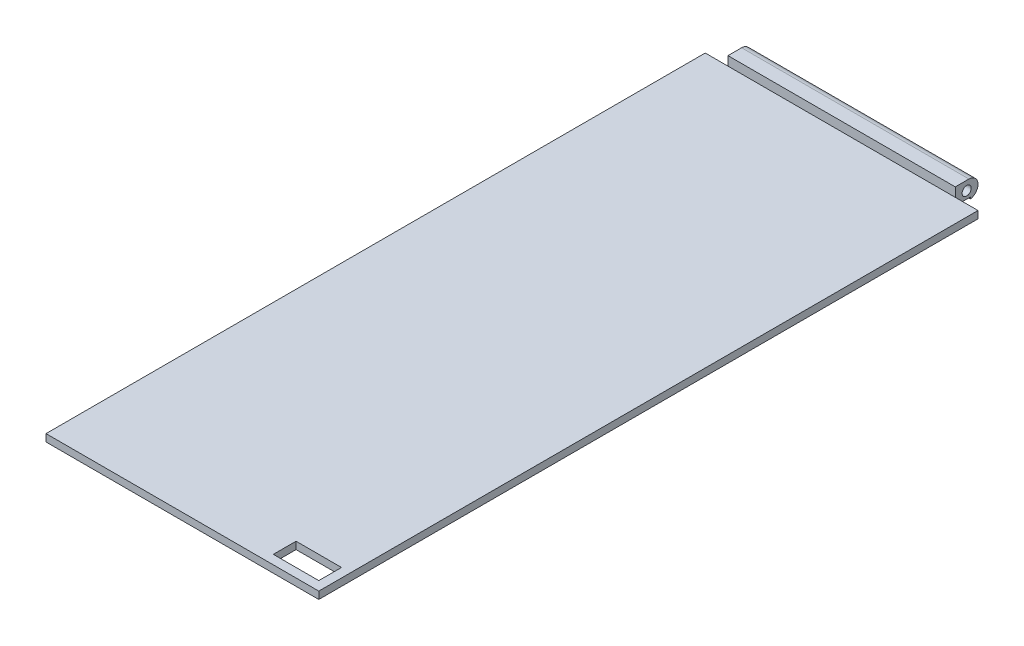
SolidWorks part; units mm, degrees
ref_plane "Front Plane" through (0, 0, 0) normal (0, 0, 1) x (1, 0, 0)
ref_plane "Top Plane" through (0, 0, 0) normal (0, 1, 0) x (1, 0, 0)
ref_plane "Right Plane" through (0, 0, 0) normal (1, 0, 0) x (0, 0, -1)
sketch "Sketch1" plane through (0, 0, 0) normal (0, 1, 0) x (1, 0, 0)
  line L1 (-15, -35) -> (15, -35)
  line L2 (-15, -35) -> (-15, 35)
  line L3 (-15, 35) -> (15, 35)
  line L4 (15, -35) -> (15, 35)
  line L5 (-15, -35) -> (15, 35) construction
  line L6 (-15, 35) -> (15, -35) construction
  point P0 (0, 0)
  dimension "D1" = 70
  dimension "D2" = 30
extrude "Boss-Extrude1" add sketch "Sketch1" along normal blind 1 contours L2 L3 L4 L1
sketch "Sketch2" plane through (0, 1, 0) normal (0, 1, 0) x (1, 0, 0)
  line L0 (15, -35) -> (15, 35) construction
  line L1 (-15, 35) -> (15, 35)
  line L2 (-15, 35) -> (-15, 32.5)
  line L3 (-15, 32.5) -> (15, 32.5)
  line L4 (15, 35) -> (15, 32.5)
  dimension "D1" = 2.5
extrude "Boss-Extrude2" add sketch "Sketch2" along normal blind 1
sketch "Sketch3" plane through (15, 0, 0) normal (1, 0, 0) x (0, 0, -1)
  line L1 (32.5, 2) -> (35, 2) construction
  line L3 (32.5, 2) -> (32.5, 1) construction
  circle A1 centre (33.75, 1) radius 0.5
  dimension "D1" = 1
  dimension "D2" = 1
  dimension "D3" = 1.25
extrude "Cut-Extrude1" cut sketch "Sketch3" against normal up to vertex (30 mm away) up to point (-15, 2, -32.5)
sketch "Sketch4" plane through (0, 0, -35) normal (0, 0, -1) x (-1, 0, 0)
  line L0 (-15, 2) -> (15, 2) construction
  line L1 (-15, 2) -> (-12.5, 2)
  line L2 (-15, 2) -> (-15, 0)
  line L3 (-15, 0) -> (-12.5, 0)
  line L4 (-12.5, 2) -> (-12.5, 0)
  line L5 (-15, 2) -> (-15, 0) construction
  line L6 (15, 0) -> (-15, 0) construction
  line L7 (0, 2) -> (0, 0) construction
  line L8 (15, 0) -> (12.5, 0)
  line L9 (12.5, 2) -> (12.5, 0)
  line L10 (15, 2) -> (12.5, 2)
  line L11 (15, 2) -> (15, 0)
  dimension "D1" = 2.5
  dimension "D2" = 2
extrude "Cut-Extrude2" cut sketch "Sketch4" against normal up to vertex (2.5 mm away) up to point (-15, 1, -32.5)
fillet "Fillet1" radius 1 1 edges at (0, 2, -35)
sketch "Sketch5" plane through (0, 0, 35) normal (0, 0, 1) x (1, 0, 0)
  line L1 (-15, 1) -> (15, 1)
  line L2 (-15, 1) -> (-15, 0)
  line L3 (-15, 0) -> (15, 0)
  line L4 (15, 1) -> (15, 0)
extrude "Boss-Extrude3" add sketch "Sketch5" along normal blind 5
fillet "Fillet2" radius 1 1 edges at (0, 0, -35)
sketch "Sketch6" plane through (0, 1, 0) normal (0, 1, 0) x (1, 0, 0)
  line L0 (15, -40) -> (15, 32.5) construction
  line L1 (9, -36.5) -> (14, -36.5)
  line L2 (9, -36.5) -> (9, -39)
  line L3 (9, -39) -> (14, -39)
  line L4 (14, -36.5) -> (14, -39)
  line L5 (15, -40) -> (-15, -40) construction
  dimension "D1" = 2.5
  dimension "D2" = 5
  dimension "D3" = 1
  dimension "D4" = 1
extrude "Cut-Extrude3" cut sketch "Sketch6" against normal up to vertex (1 mm away) up to point (15, 0, 40)
sketch "Sketch7" plane through (0, 0, 0) normal (0, -1, 0) x (1, 0, 0)
  line L1 (-15, 40) -> (15, 40)
  line L2 (-15, 40) -> (-15, -34.1582)
  line L3 (-15, -34.1582) -> (15, -34.1582)
  line L4 (15, 40) -> (15, -34.1582)
extrude "Cut-Extrude4" cut sketch "Sketch7" against normal blind 0.2
